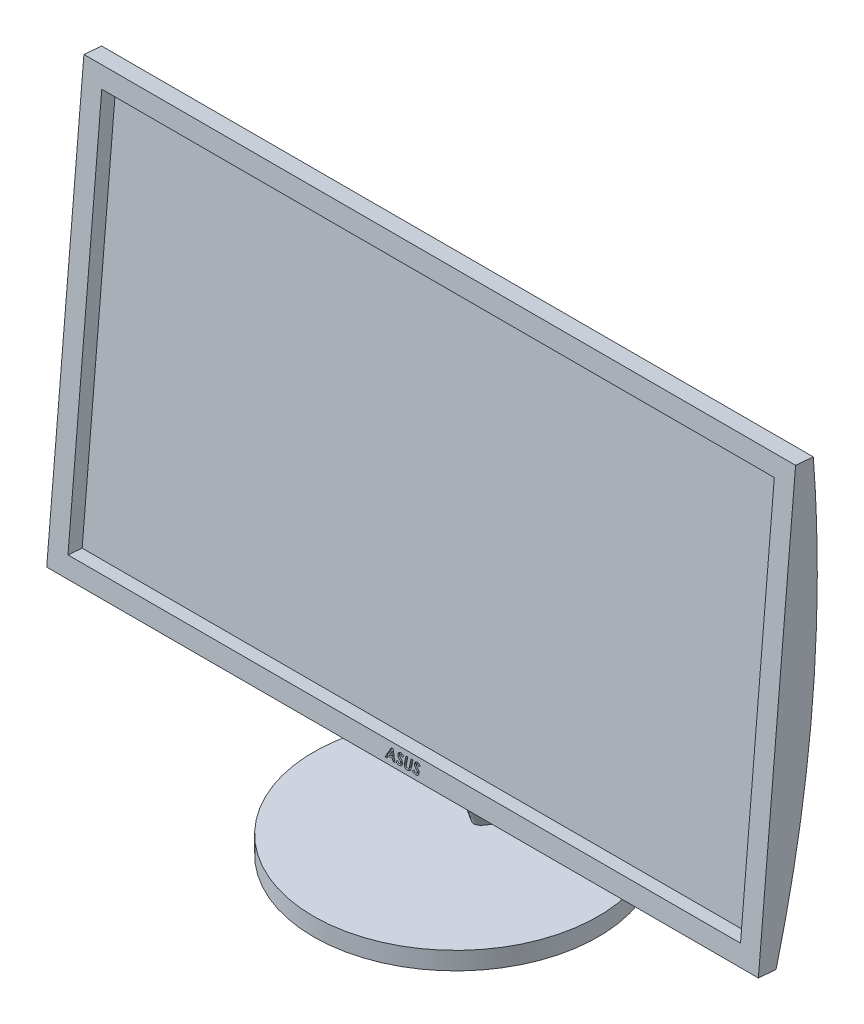
SolidWorks part; units mm, degrees
note: The reader was unsure of these and kept them because the rebuilt part matched: shared geometry of "Sketch5<2>".
ref_plane "Front Plane" through (0, 0, 0) normal (0, 0, 1) x (1, 0, 0)
ref_plane "Top Plane" through (0, 0, 0) normal (0, 1, 0) x (1, 0, 0)
ref_plane "Right Plane" through (0, 0, 0) normal (1, 0, 0) x (0, 0, -1)
sketch "Sketch1" plane through (0, 0, 0) normal (0, 1, 0) x (1, 0, 0)
  circle A0 centre (0, 0) radius 101.6
  dimension "D1" = 203.2
extrude "Boss-Extrude1" add sketch "Sketch1" along normal blind 12.7
sketch "Sketch2" plane through (0, 0, 0) normal (1, 0, 0) x (0, 0, -1)
  line L0 (-38.1, 69.85) -> (-11.5349, 373.4901)
  line L1 (-38.1, 69.85) -> (-25.4483, 68.7431)
  line L2 (-11.5349, 373.4901) -> (1.1167, 372.3833)
  line L3 (-24.8175, 221.6701) -> (69.9315, 213.3806) construction
  line L4 (101.6, 12.7) -> (-101.6, 12.7) construction
  spline S0 degree 2 poles (1.1167, 372.3833) (13.1376, 218.3494) (-25.4483, 68.7431) knots 0 0 0 1 1 1
  point P8 (0, 0)
  point P10 (0, 0)
  point P11 (0, 0)
  dimension "D1" = 5
  dimension "D2" = 12.7
  dimension "D3" = 25.4
  dimension "D4" = 57.15
  dimension "D5" = 38.1
  dimension "D6" = 304.8
extrude "Boss-Extrude2" add sketch "Sketch2" along normal mid plane 508 separate body
sketch "Sketch3" plane through (0, 3.8386, 43.8753) normal (0, 0.0872, 0.9962) x (1, 0, 0)
  line L12 (-240.03, 357.0936) -> (-240.03, 80.2336)
  line L13 (-240.03, 80.2336) -> (240.03, 80.2336)
  line L14 (240.03, 80.2336) -> (240.03, 357.0936)
  line L15 (240.03, 357.0936) -> (-240.03, 357.0936)
  line L16 (-240.03, 357.0936) -> (-240.03, 80.2336)
  line L17 (-240.03, 80.2336) -> (240.03, 80.2336)
  line L18 (240.03, 80.2336) -> (240.03, 357.0936)
  line L19 (240.03, 357.0936) -> (-240.03, 357.0936)
  point P0 (0, 0)
  dimension "D1" = 13.97
extrude "Cut-Extrude1" cut sketch "Sketch3" against normal blind 10.16
sketch "Sketch4" plane through (0, 12.7, 0) normal (0, 1, 0) x (1, 0, 0)
  line L0 (0, 82.55) -> (0, 0) construction
  spline S0 degree 2 poles (-19.9466, 69.85) (0, 95.25) (19.9466, 69.85) knots 0 0 0 1 1 1
  spline S1 degree 2 poles (-19.9466, 69.85) (0, -44.45) (19.9466, 69.85) knots 0 0 0 1 1 1
  point P4 (0, 0)
  point P5 (-20.1186, 76.1781)
  point P7 (0, 0)
  point P8 (0, 0)
  point P9 (0, 0)
  point P12 (-20.6441, 64.0328)
  point P13 (-16.7154, 72.9151)
  point P14 (0, 0)
  dimension "D1" = 39.8932
  dimension "D2" = 69.85
  dimension "D3" = 12.7
  dimension "D4" = 12.7
ref_plane "Plane1" through (0, 1.6248, 18.5719) normal (0, -0.0872, -0.9962) x (-1, 0, 0)
sketch "Sketch5" plane through (0, 1.6248, 18.5719) normal (0, -0.0872, -0.9962) x (-1, 0, 0)
  line L0 (0, 0) -> (0, 235.2692) construction
  line L1 (-254, 66.2636) -> (254, 66.2636) construction
  spline S0 degree 2 poles (-19.05, 104.3636) (0, 129.7636) (19.05, 104.3636) knots 0 0 0 1 1 1
  spline S1 degree 2 poles (-19.05, 104.3636) (0, 53.5636) (19.05, 104.3636) knots 0 0 0 1 1 1
  point P7 (0, 0)
  point P8 (0, 0)
  point P9 (0, 0)
  point P10 (0, 0)
  point P11 (0, 93.5934)
  dimension "D1" = 12.7
  dimension "D2" = 38.1
  dimension "D3" = 38.1
  dimension "D4" = 12.7
extrude "Boss-Extrude3" add sketch "Sketch5" along direction (0, 0.0872, 0.9962) on the side against the normal up to surface (15.24 mm away)
loft "Loft1" add profiles "Sketch4", "Sketch5<2>"
sketch "Sketch5<2>" plane through (0, 1.6248, 18.5719) normal (0, -0.0872, -0.9962) x (-1, 0, 0) same geometry as "Sketch5"
sketch "Sketch6" plane through (0, 3.8386, 43.8753) normal (0, 0.0872, 0.9962) x (1, 0, 0)
  line L0 (0, 0) -> (0, 115.216) construction
  line L1 (-35.0315, 69.4386) -> (50.7658, 69.4386) construction
  line L2 (254, 66.2636) -> (-254, 66.2636) construction
  text T0 "ASUS" font "Century Gothic" height in points 28
  point P8 (0, 0)
  dimension "D1" = 3.175
  dimension "D2" = 12.7
extrude "Cut-Extrude2" cut sketch "Sketch6" along direction (0, -0.0872, -0.9962) on the side against the normal blind 1.27
